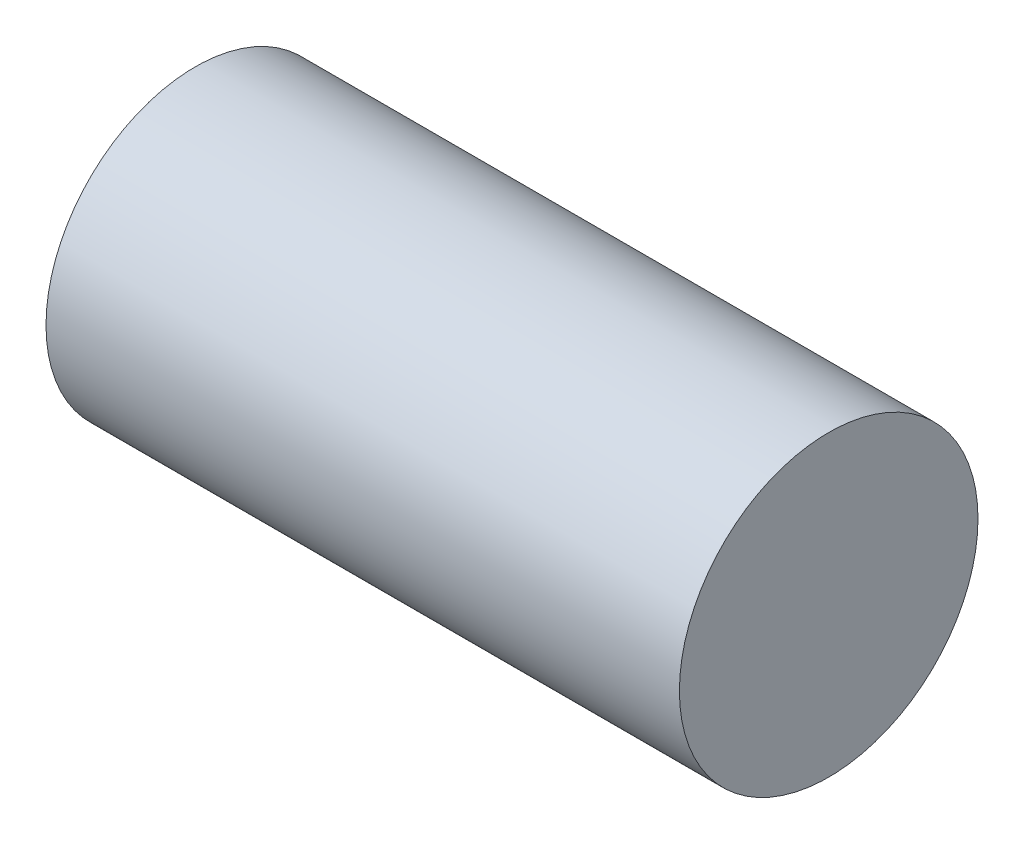
SolidWorks part; units mm, degrees
ref_plane "Front Plane" through (0, 0, 0) normal (0, 0, 1) x (1, 0, 0)
ref_plane "Top Plane" through (0, 0, 0) normal (0, 1, 0) x (1, 0, 0)
ref_plane "Right Plane" through (0, 0, 0) normal (1, 0, 0) x (0, 0, -1)
sketch "Sketch1" plane through (0, 0, 0) normal (1, 0, 0) x (0, 0, -1)
  circle A0 centre (0, 0) radius 16.5
  dimension "D1" = 33
extrude "Boss-Extrude1" add sketch "Sketch1" along normal blind 35 and the other way blind 35 contours A0 region at (0, 0, 0)
